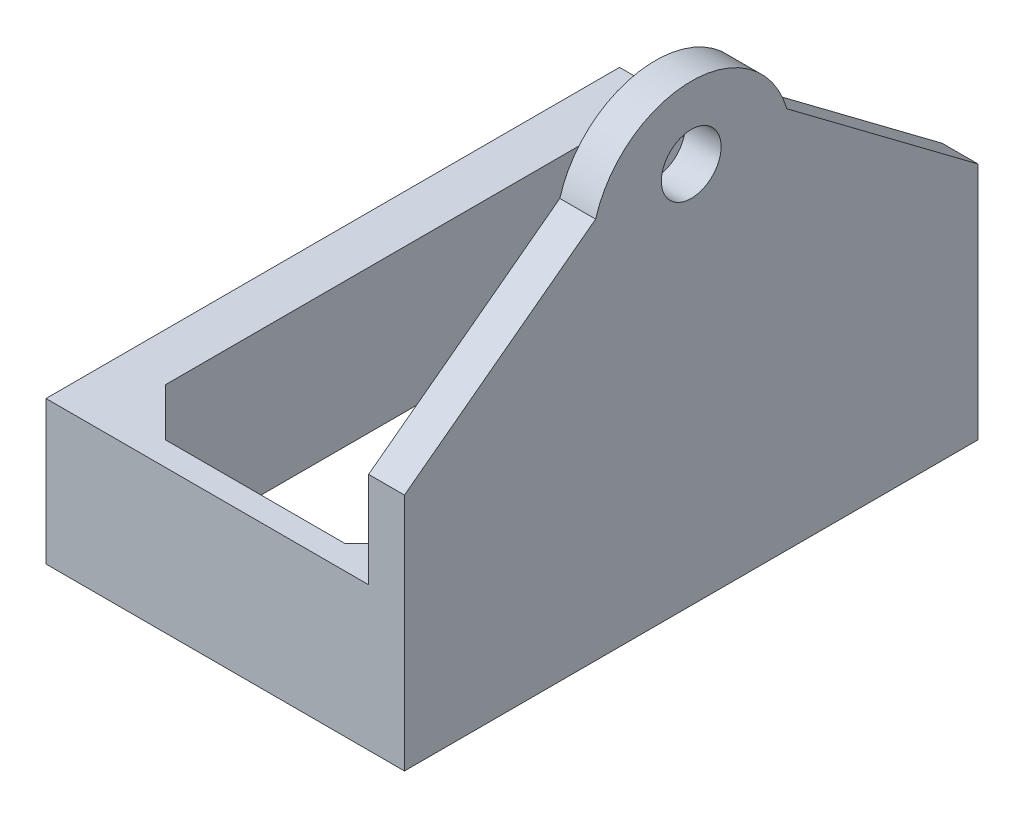
SolidWorks part; units mm, degrees
note: The reader was unsure of these and kept them because the rebuilt part matched: shared geometry of "Sketch1<4>", "Sketch4<3>".
ref_plane "Front Plane" through (0, 0, 0) normal (0, 0, 1) x (1, 0, 0)
ref_plane "Top Plane" through (0, 0, 0) normal (0, 1, 0) x (1, 0, 0)
ref_plane "Right Plane" through (0, 0, 0) normal (1, 0, 0) x (0, 0, -1)
sketch "Sketch1" plane through (0, 0, 0) normal (0, 1, 0) x (1, 0, 0)
  line L0 (19.05, 38.1) -> (19.05, -38.1)
  line L1 (23.8125, -38.1) -> (-23.8125, -38.1)
  line L2 (23.8125, -38.1) -> (23.8125, 38.1)
  line L3 (23.8125, 38.1) -> (-23.8125, 38.1)
  line L4 (-23.8125, -38.1) -> (-23.8125, 38.1)
  line L5 (23.8125, -38.1) -> (-23.8125, 38.1) construction
  line L6 (23.8125, 38.1) -> (-23.8125, -38.1) construction
  line L8 (19.05, 34.925) -> (-17.4625, 34.925)
  line L9 (19.05, 34.925) -> (19.05, -34.925)
  line L10 (19.05, -34.925) -> (-17.4625, -34.925)
  line L11 (-17.4625, 34.925) -> (-17.4625, -34.925)
  line L12 (19.05, 34.925) -> (-17.4625, -34.925) construction
  line L13 (19.05, -34.925) -> (-17.4625, 34.925) construction
  point P0 (0, 0)
  point P8 (0.7938, 0)
  dimension "D1" = 47.625
  dimension "D2" = 76.2
  dimension "D3" = 4.7625
  dimension "D4" = 36.5125
  dimension "D5" = 69.85
  dimension "D6" = 6.35
extrude "Boss-Extrude1" add sketch "Sketch1" along normal blind 6.35 contours L4 L1 L0 L3
extrude "Boss-Extrude2" add sketch "Sketch1<4>" along normal blind 60.325 contours L2 L3 L0 L1
sketch "Sketch1<4>" plane through (0, 0, 0) normal (0, 1, 0) x (1, 0, 0) same geometry as "Sketch1"
sketch "Sketch2" plane through (0, 6.35, 0) normal (0, 1, 0) x (1, 0, 0)
  line L0 (19.05, -38.1) -> (-23.8125, -38.1) construction
  line L1 (-23.8125, 38.1) -> (-17.4625, 38.1)
  line L2 (-23.8125, 38.1) -> (-23.8125, -38.1)
  line L3 (-23.8125, -38.1) -> (-17.4625, -38.1)
  line L4 (-17.4625, 38.1) -> (-17.4625, -38.1)
  dimension "D1" = 6.35
extrude "Boss-Extrude3" add sketch "Sketch2" along normal blind 12.7
sketch "Sketch4" plane through (23.8125, 0, 0) normal (1, 0, 0) x (0, 0, -1)
  line L0 (-38.1, 0) -> (38.1, 0) construction
  line L1 (-38.1, 6.35) -> (38.1, 6.35) construction
  line L2 (-38.1, 60.325) -> (-38.1, 0) construction
  line L3 (38.1, 60.325) -> (38.1, 0) construction
  line L4 (38.1, 50.8) -> (-38.1, 50.8) construction
  line L5 (0, 60.325) -> (0, 0) construction
  line L6 (-38.1, 60.325) -> (38.1, 60.325) construction
  line L7 (-38.1, 31.75) -> (38.1, 31.75) construction
  line L8 (-38.1, 31.75) -> (-12.7, 50.8)
  line L9 (-38.1, 31.75) -> (-38.1, 60.325)
  line L10 (-38.1, 60.325) -> (0, 60.325)
  line L11 (0, 60.325) -> (38.1, 60.325)
  line L12 (38.1, 60.325) -> (38.1, 31.75)
  line L13 (12.7, 50.8) -> (38.1, 31.75)
  circle A0 centre (0, 50.8) radius 3.9688
  arc A1 (-12.7, 50.8) -> (12.7, 50.8) centre (0, 47.0958) cw
  point P2 (0, 0)
  point P14 (-12.7, 50.8)
  point P19 (12.7, 50.8)
  dimension "D1" = 50.8
  dimension "D2" = 6.35
  dimension "D3" = 12.7
  dimension "D4" = 25.4
extrude "Cut-Extrude2" cut sketch "Sketch4" against normal up to next
extrude "Cut-Extrude3" cut sketch "Sketch4<3>" against normal up to next contours A0
sketch "Sketch4<3>" plane through (23.8125, 0, 0) normal (1, 0, 0) x (0, 0, -1) same geometry as "Sketch4"
sketch "Sketch7" plane through (0, 6.35, 0) normal (0, 1, 0) x (1, 0, 0)
  line L0 (-17.4625, 0) -> (19.05, 0) construction
  line L1 (-17.4625, -38.1) -> (-17.4625, -34.925) construction
  line L2 (19.05, 38.1) -> (19.05, 34.925) construction
  line L3 (-17.4625, 34.925) -> (19.05, 34.925)
  line L4 (-17.4625, -38.1) -> (19.05, -38.1)
  line L5 (-17.4625, -38.1) -> (-17.4625, -34.925)
  line L6 (-17.4625, -34.925) -> (19.05, -34.925)
  line L7 (19.05, -38.1) -> (19.05, -34.925)
  line L8 (19.05, 38.1) -> (19.05, 34.925)
  line L9 (-17.4625, 38.1) -> (19.05, 38.1)
  line L10 (-17.4625, 38.1) -> (-17.4625, 34.925)
  dimension "D1" = 3.175
extrude "Boss-Extrude5" add sketch "Sketch7" along normal blind 12.7
chamfer "Chamfer6" distance 6.35 angle 45 4 edges at (19.05, 9.525, -34.925) (19.05, 9.525, 34.925) (-17.4625, 9.525, 34.925) (-17.4625, 9.525, -34.925)
